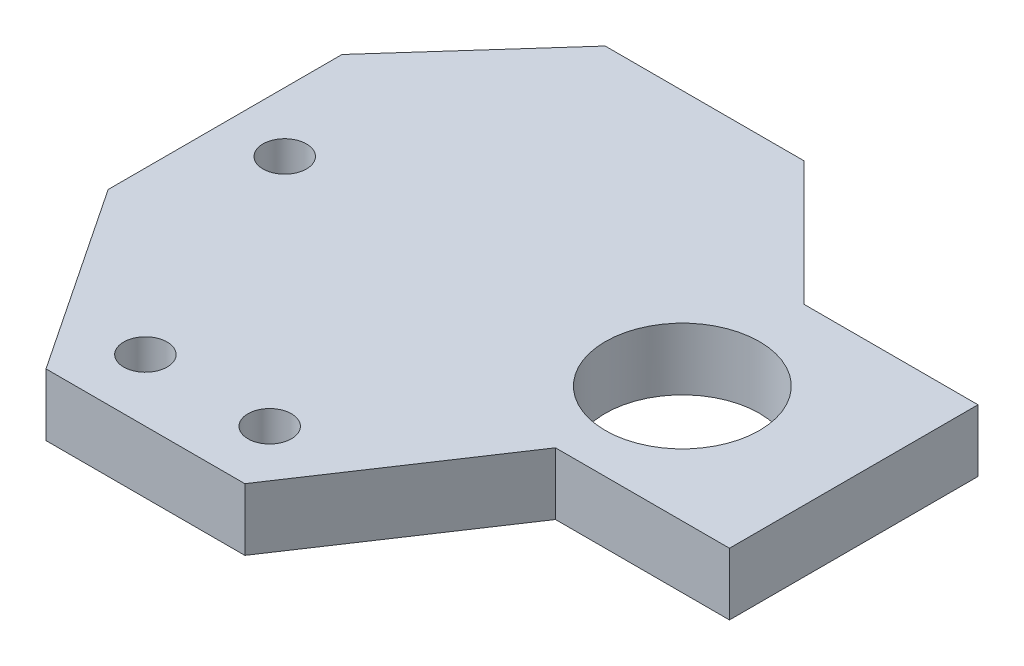
SolidWorks part; units mm, degrees
ref_plane "Front Plane" through (0, 0, 0) normal (0, 0, 1) x (1, 0, 0)
ref_plane "Top Plane" through (0, 0, 0) normal (0, 1, 0) x (1, 0, 0)
ref_plane "Right Plane" through (0, 0, 0) normal (1, 0, 0) x (0, 0, -1)
sketch "Sketch1" plane through (0, 0, 0) normal (0, 1, 0) x (1, 0, 0)
  line L0 (0, 33.8197) -> (10, 45)
  line L1 (0, 0) -> (50, 0)
  line L2 (0, 0) -> (0, 45)
  line L3 (0, 45) -> (50, 45)
  line L4 (50, 0) -> (50, 45)
  line L5 (0, 15) -> (10, 0)
  line L6 (26, 45) -> (36, 35)
  line L7 (26, 0) -> (36, 15)
  line L8 (36, 15) -> (50, 15)
  line L9 (36, 35) -> (50, 35)
  line L10 (50, 25) -> (0, 25) construction
  circle A1 centre (13, 5) radius 1.75
  circle A2 centre (23, 5) radius 1.75
  dimension "D15" = 10
  dimension "D16" = 3.5
  dimension "D24" = 3
  dimension "D25" = 3
  dimension "D17" = 3.5
  dimension "D1" = 45
  dimension "D2" = 50
  dimension "D3" = 15
  dimension "D4" = 10
  dimension "D5" = 10
  dimension "D6" = 15
  dimension "D7" = 16
  dimension "D8" = 16
  dimension "D9" = 10
  dimension "D10" = 10
  dimension "D11" = 10
  dimension "D12" = 20
  dimension "D13" = 10
  dimension "D18" = 5
extrude "Boss-Extrude1" add sketch "Sketch1" along normal blind 5 contours L4 L10 L2 L5 L1 L7 L8 | L10 L4 L9 L6 L3 L0 L2 | L10 | L10 region at (22.3613, 0, -23.5179)
ref_plane "Plane1" through (0, 0, 0) normal (0, -1, 0) x (-1, 0, 0)
sketch "Sketch2" plane through (0, 0, 0) normal (0, -1, 0) x (-1, 0, 0)
  line L0 (0, 24.4098) -> (-68.9029, 24.4098) construction
  line L1 (0, 15) -> (0, 33.8197) construction
  circle A0 centre (-4.8, 24.4098) radius 1.75
  circle A1 centre (-36.8, 24.4098) radius 6.2
  dimension "D1" = 4.8
  dimension "D2" = 12.4
  dimension "D3" = 32
extrude "Cut-Extrude1" cut sketch "Sketch2" against normal blind 10
